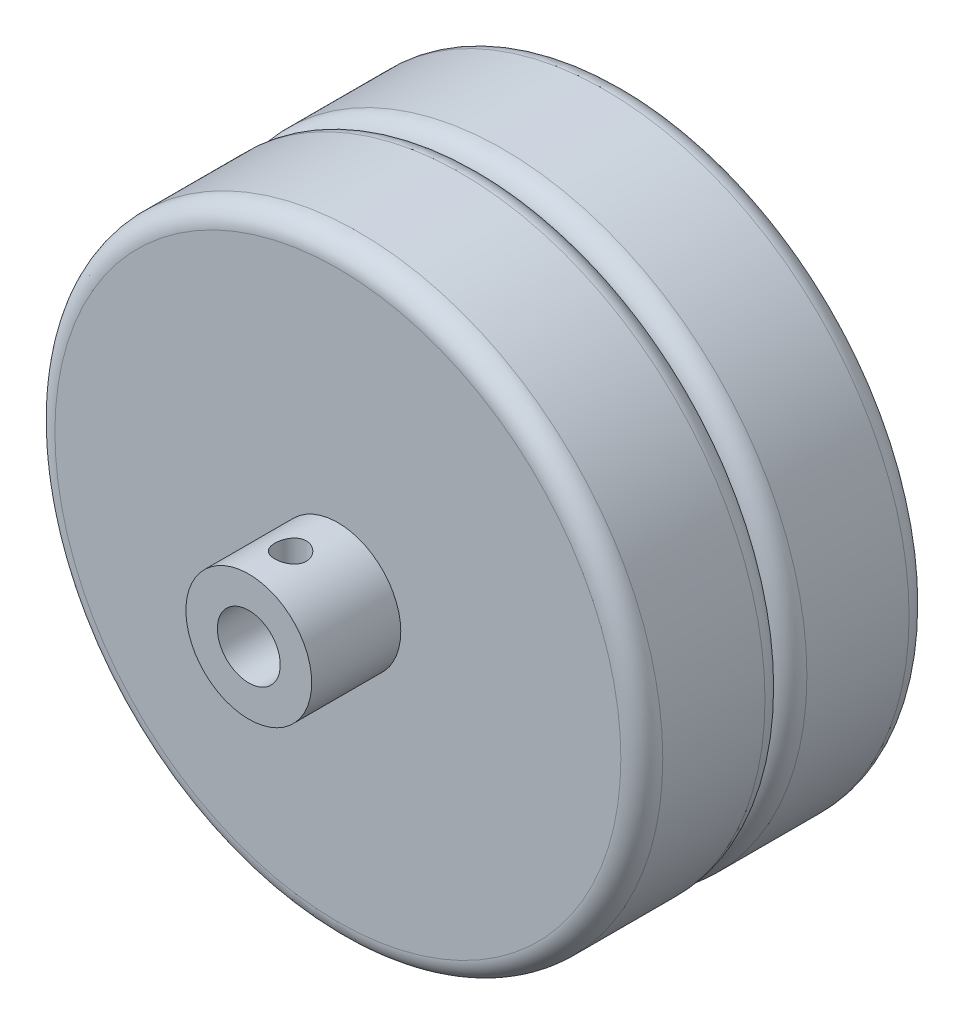
SolidWorks part; units mm, degrees
ref_plane "前视基准面" through (0, 0, 0) normal (0, 0, 1) x (1, 0, 0)
ref_plane "上视基准面" through (0, 0, 0) normal (0, 1, 0) x (1, 0, 0)
ref_plane "右视基准面" through (0, 0, 0) normal (1, 0, 0) x (0, 0, -1)
sketch "草图1" plane through (0, 0, 0) normal (0, 0, 1) x (1, 0, 0)
  circle A0 centre (0, 0) radius 29
  dimension "D1" = 58
extrude "凸台-拉伸1" add sketch "草图1" along normal blind 13.75
fillet "圆角1" radius 2 1 edges at (29, 0, 13.75)
fillet "圆角2" radius 2 1 edges at (29, 0, 0)
sketch "草图2" plane through (0, 0, 13.75) normal (0, 0, 1) x (1, 0, 0)
  circle A0 centre (0, 0) radius 29
  dimension "D1" = 58
extrude "凸台-拉伸2" add sketch "草图2" along normal blind 13.75
fillet "圆角3" radius 2 2 edges at (29, 0, 13.75) (29, 0, 27.5)
sketch "草图4" plane through (0, 0, 27.5) normal (0, 0, 1) x (1, 0, 0)
  circle A0 centre (0, 0) radius 6
  dimension "D1" = 12
extrude "切除-拉伸1" cut sketch "草图4" against normal blind 24
sketch "草图10" plane through (0, 0, 27.5) normal (0, 0, 1) x (1, 0, 0)
  circle A0 centre (0, 0) radius 6
  circle A1 centre (0, 0) radius 3
extrude "凸台-拉伸3" add sketch "草图10" along normal blind 8.5 separate body
ref_plane "基准面1" through (0, 6, 0) normal (0, 1, 0) x (1, 0, 0)
sketch "草图11" plane through (0, 6, 0) normal (0, 1, 0) x (1, 0, 0)
  circle A0 centre (0, -32.015) radius 1.5
  point P2 (0, -32.015)
  dimension "D1" = 3
extrude "切除-拉伸2" cut sketch "草图11" against normal blind 5
